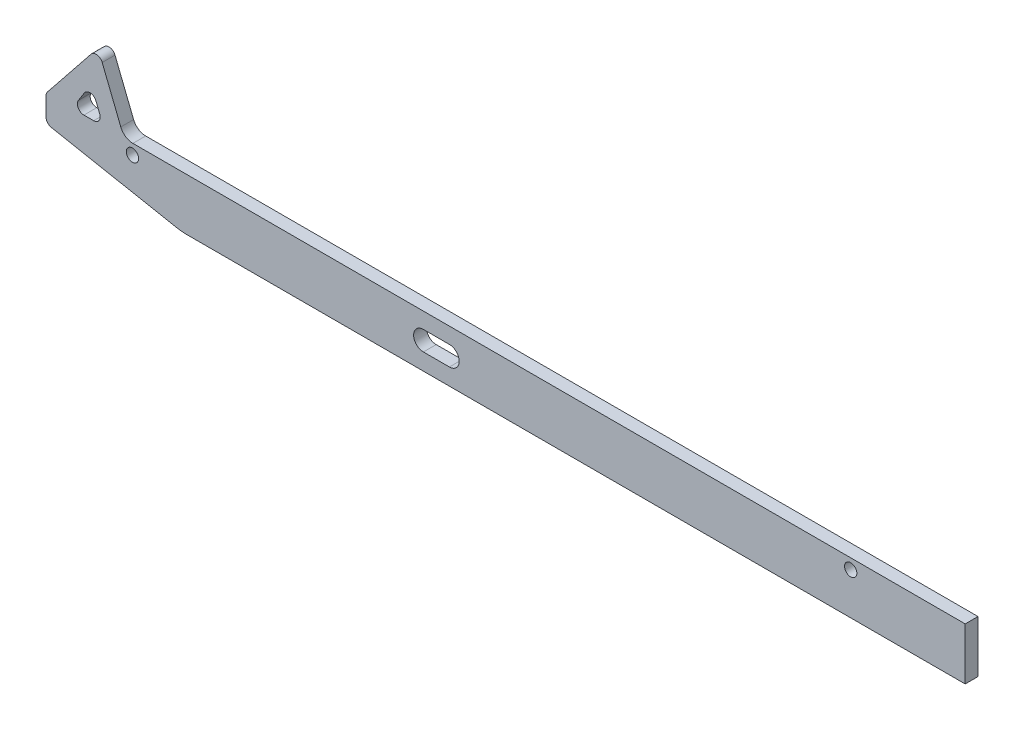
SolidWorks part; units mm, degrees
ref_plane "Front Plane" through (0, 0, 0) normal (0, 0, 1) x (1, 0, 0)
ref_plane "Top Plane" through (0, 0, 0) normal (0, 1, 0) x (1, 0, 0)
ref_plane "Right Plane" through (0, 0, 0) normal (1, 0, 0) x (0, 0, -1)
sketch "Sketch1" plane through (0, 0, 0) normal (0, 0, 1) x (1, 0, 0)
  line L0 (-110.4919, 6.2563) -> (-110.4919, 38.0063) construction
  line L1 (113.7998, -6.4437) -> (-77.3725, -6.4437)
  line L2 (113.7998, -6.4437) -> (113.7998, 6.2563)
  line L3 (113.7998, 6.2563) -> (-91.4419, 6.2563)
  line L4 (-97.7919, 22.1313) -> (-110.4919, 6.2563)
  line L5 (113.7998, -6.4437) -> (-110.4919, 6.2563) construction
  line L6 (113.7998, 6.2563) -> (-117.2068, -6.4437) construction
  line L7 (-110.4919, 38.0063) -> (-104.1419, 38.0063) construction
  line L8 (-110.4919, -0.0937) -> (-77.3725, -6.4437)
  line L9 (-104.1419, 38.0063) -> (-97.7919, 22.1313) construction
  line L10 (-104.1419, 6.2563) -> (-104.1419, 25.3063) construction
  line L11 (-104.1419, 25.3063) -> (-96.5219, 6.2563) construction
  line L12 (-104.1419, 6.2563) -> (-100.3319, 15.7813) construction
  line L13 (-100.3319, 15.7813) -> (-97.7919, 22.1313) construction
  line L14 (-110.4919, 6.2563) -> (-110.4919, -0.0937)
  line L15 (-97.7919, 22.1313) -> (-91.4419, 6.2563)
  line L16 (-104.1419, 6.2563) -> (-99.4608, 13.6034)
  line L17 (-99.4608, 13.6034) -> (-96.5219, 6.2563)
  line L18 (-96.5219, 6.2563) -> (-104.1419, 6.2563)
  line L19 (-97.7919, 22.1313) -> (-91.4419, 6.2563) construction
  point P0 (0, 0)
  dimension "D1" = 6.35
  dimension "D2" = 224.2918
  dimension "D3" = 6.35
  dimension "D5" = 31.75
  dimension "D6" = 19.05
  dimension "D7" = 6.35
  dimension "D9" = 12.7
extrude "Boss-Extrude1" add sketch "Sketch1" along normal blind 3.1242
fillet "Fillet4" radius 12.7 1 edges at (-77.3725, -6.4437, 1.5621)
fillet "Fillet8" radius 1.5875 6 edges at (-110.4919, -0.0937, 1.5621) (-110.4919, 6.2563, 1.5621) (-97.7919, 22.1313, 1.5621) (-99.4608, 13.6034, 1.5621) (-104.1419, 6.2563, 1.5621) (-96.5219, 6.2563, 1.5621)
fillet "Fillet9" radius 3.175 1 edges at (-91.4419, 6.2563, 1.5621)
sketch "Sketch2" plane through (0, 0, 3.1242) normal (0, 0, 1) x (1, 0, 0)
  line L0 (-18.4072, 0) -> (-12.0572, 0) construction
  line L1 (-18.4072, 2.3813) -> (-12.0572, 2.3813)
  line L2 (-18.4072, -2.3813) -> (-12.0572, -2.3813)
  line L4 (113.7998, -6.4437) -> (113.7998, 6.2563) construction
  arc A0 (-18.4072, 2.3813) -> (-18.4072, -2.3813) centre (-18.4072, 0) ccw
  arc A1 (-12.0572, -2.3813) -> (-12.0572, 2.3813) centre (-12.0572, 0) ccw
  point P3 (-15.2322, 0)
  point P8 (113.7998, -0.0937)
  dimension "D2" = 2.3813
  dimension "D1" = 6.35
  dimension "D3" = 129.032
extrude "Cut-Extrude1" cut sketch "Sketch2" against normal through all
sketch "Sketch3" plane through (0, 0, 3.1242) normal (0, 0, 1) x (1, 0, 0)
  line L0 (113.7998, 3.7163) -> (0, 3.7163) construction
  line L2 (-76.166, -6.4437) -> (113.7998, -6.4437) construction
  line L3 (113.7998, -6.4437) -> (113.7998, 6.2563) construction
  circle A0 centre (85.8598, 3.7163) radius 1.5
  circle A1 centre (-89.4002, 3.7163) radius 1.5
  dimension "D1" = 3
  dimension "D4" = 3
  dimension "D2" = 27.94
  dimension "D3" = 10.16
  dimension "D5" = 203.2
extrude "Cut-Extrude2" cut sketch "Sketch3" against normal through all
